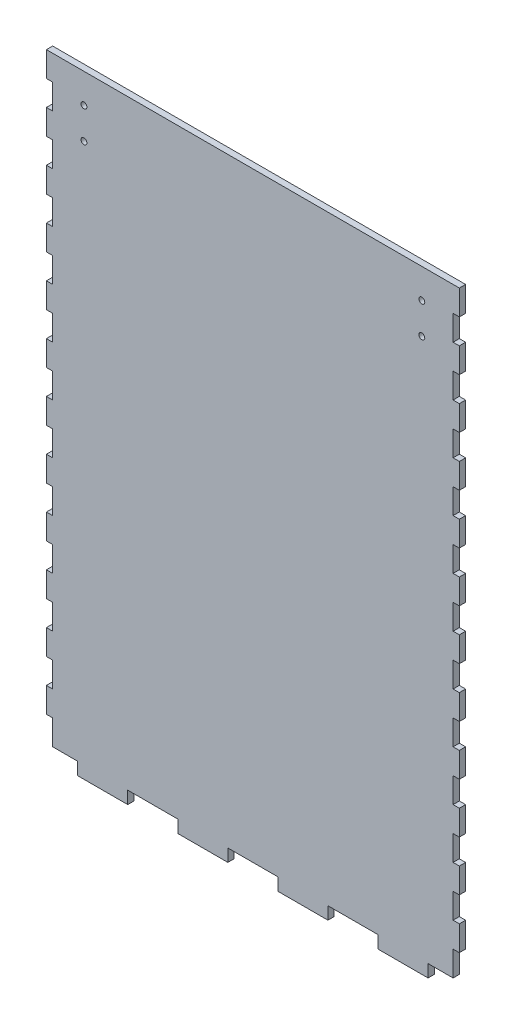
SolidWorks part; units mm, degrees
ref_plane "Front Plane" through (0, 0, 0) normal (0, 0, 1) x (1, 0, 0)
ref_plane "Top Plane" through (0, 0, 0) normal (0, 1, 0) x (1, 0, 0)
ref_plane "Right Plane" through (0, 0, 0) normal (1, 0, 0) x (0, 0, -1)
sketch "Sketch1" plane through (0, 0, 0) normal (0, 0, 1) x (1, 0, 0)
  line L0 (0, 0) -> (203.2, 0)
  line L1 (203.2, 0) -> (203.2, 304.8)
  line L2 (203.2, 304.8) -> (0, 304.8)
  line L3 (0, 304.8) -> (0, 0)
  dimension "D1" = 203.2
  dimension "D2" = 304.8
extrude "Boss-Extrude1" add sketch "Sketch1" along normal blind 3.175
sketch "Sketch2" plane through (0, 0, 3.175) normal (0, 0, 1) x (1, 0, 0)
  line L0 (0, 304.8) -> (-3.175, 304.8)
  line L1 (-3.175, 304.8) -> (-3.175, 292.1)
  line L2 (-3.175, 292.1) -> (0, 292.1)
  line L3 (0, 304.8) -> (0, 0) construction
  line L4 (0, 292.1) -> (0, 304.8)
  line L5 (101.6, 304.8) -> (101.6, 0) construction
  line L6 (203.2, 304.8) -> (0, 304.8) construction
  line L7 (0, 0) -> (203.2, 0) construction
  line L8 (206.375, 292.1) -> (203.2, 292.1)
  line L9 (206.375, 304.8) -> (206.375, 292.1)
  line L10 (203.2, 304.8) -> (206.375, 304.8)
  line L11 (203.2, 292.1) -> (203.2, 304.8)
  line L12 (0, 266.7) -> (0, 279.4)
  line L13 (0, 279.4) -> (-3.175, 279.4)
  line L14 (-3.175, 279.4) -> (-3.175, 266.7)
  line L15 (-3.175, 266.7) -> (0, 266.7)
  line L16 (206.375, 266.7) -> (203.2, 266.7)
  line L17 (203.2, 266.7) -> (203.2, 279.4)
  line L18 (203.2, 279.4) -> (206.375, 279.4)
  line L19 (206.375, 279.4) -> (206.375, 266.7)
  line L20 (0, 241.3) -> (0, 254)
  line L21 (0, 254) -> (-3.175, 254)
  line L22 (-3.175, 254) -> (-3.175, 241.3)
  line L23 (-3.175, 241.3) -> (0, 241.3)
  line L24 (206.375, 241.3) -> (203.2, 241.3)
  line L25 (203.2, 241.3) -> (203.2, 254)
  line L26 (203.2, 254) -> (206.375, 254)
  line L27 (206.375, 254) -> (206.375, 241.3)
  line L28 (0, 215.9) -> (0, 228.6)
  line L29 (0, 228.6) -> (-3.175, 228.6)
  line L30 (-3.175, 228.6) -> (-3.175, 215.9)
  line L31 (-3.175, 215.9) -> (0, 215.9)
  line L32 (206.375, 215.9) -> (203.2, 215.9)
  line L33 (203.2, 215.9) -> (203.2, 228.6)
  line L34 (203.2, 228.6) -> (206.375, 228.6)
  line L35 (206.375, 228.6) -> (206.375, 215.9)
  line L36 (0, 190.5) -> (0, 203.2)
  line L37 (0, 203.2) -> (-3.175, 203.2)
  line L38 (-3.175, 203.2) -> (-3.175, 190.5)
  line L39 (-3.175, 190.5) -> (0, 190.5)
  line L40 (206.375, 190.5) -> (203.2, 190.5)
  line L41 (203.2, 190.5) -> (203.2, 203.2)
  line L42 (203.2, 203.2) -> (206.375, 203.2)
  line L43 (206.375, 203.2) -> (206.375, 190.5)
  line L44 (0, 165.1) -> (0, 177.8)
  line L45 (0, 177.8) -> (-3.175, 177.8)
  line L46 (-3.175, 177.8) -> (-3.175, 165.1)
  line L47 (-3.175, 165.1) -> (0, 165.1)
  line L48 (206.375, 165.1) -> (203.2, 165.1)
  line L49 (203.2, 165.1) -> (203.2, 177.8)
  line L50 (203.2, 177.8) -> (206.375, 177.8)
  line L51 (206.375, 177.8) -> (206.375, 165.1)
  line L52 (0, 139.7) -> (0, 152.4)
  line L53 (0, 152.4) -> (-3.175, 152.4)
  line L54 (-3.175, 152.4) -> (-3.175, 139.7)
  line L55 (-3.175, 139.7) -> (0, 139.7)
  line L56 (206.375, 139.7) -> (203.2, 139.7)
  line L57 (203.2, 139.7) -> (203.2, 152.4)
  line L58 (203.2, 152.4) -> (206.375, 152.4)
  line L59 (206.375, 152.4) -> (206.375, 139.7)
  line L60 (0, 114.3) -> (0, 127)
  line L61 (0, 127) -> (-3.175, 127)
  line L62 (-3.175, 127) -> (-3.175, 114.3)
  line L63 (-3.175, 114.3) -> (0, 114.3)
  line L64 (206.375, 114.3) -> (203.2, 114.3)
  line L65 (203.2, 114.3) -> (203.2, 127)
  line L66 (203.2, 127) -> (206.375, 127)
  line L67 (206.375, 127) -> (206.375, 114.3)
  line L68 (0, 88.9) -> (0, 101.6)
  line L69 (0, 101.6) -> (-3.175, 101.6)
  line L70 (-3.175, 101.6) -> (-3.175, 88.9)
  line L71 (-3.175, 88.9) -> (0, 88.9)
  line L72 (206.375, 88.9) -> (203.2, 88.9)
  line L73 (203.2, 88.9) -> (203.2, 101.6)
  line L74 (203.2, 101.6) -> (206.375, 101.6)
  line L75 (206.375, 101.6) -> (206.375, 88.9)
  line L76 (0, 63.5) -> (0, 76.2)
  line L77 (0, 76.2) -> (-3.175, 76.2)
  line L78 (-3.175, 76.2) -> (-3.175, 63.5)
  line L79 (-3.175, 63.5) -> (0, 63.5)
  line L80 (206.375, 63.5) -> (203.2, 63.5)
  line L81 (203.2, 63.5) -> (203.2, 76.2)
  line L82 (203.2, 76.2) -> (206.375, 76.2)
  line L83 (206.375, 76.2) -> (206.375, 63.5)
  line L84 (0, 38.1) -> (0, 50.8)
  line L85 (0, 50.8) -> (-3.175, 50.8)
  line L86 (-3.175, 50.8) -> (-3.175, 38.1)
  line L87 (-3.175, 38.1) -> (0, 38.1)
  line L88 (206.375, 38.1) -> (203.2, 38.1)
  line L89 (203.2, 38.1) -> (203.2, 50.8)
  line L90 (203.2, 50.8) -> (206.375, 50.8)
  line L91 (206.375, 50.8) -> (206.375, 38.1)
  line L92 (0, 12.7) -> (0, 25.4)
  line L93 (0, 25.4) -> (-3.175, 25.4)
  line L94 (-3.175, 25.4) -> (-3.175, 12.7)
  line L95 (-3.175, 12.7) -> (0, 12.7)
  line L96 (206.375, 12.7) -> (203.2, 12.7)
  line L97 (203.2, 12.7) -> (203.2, 25.4)
  line L98 (203.2, 25.4) -> (206.375, 25.4)
  line L99 (206.375, 25.4) -> (206.375, 12.7)
  line L100 (0, 292.1) -> (0, 266.7) construction
  line L101 (12.7, 0) -> (12.7, -6.35)
  line L102 (12.7, -6.35) -> (38.1, -6.35)
  line L103 (38.1, -6.35) -> (38.1, 0)
  line L104 (38.1, 0) -> (12.7, 0)
  line L105 (88.9, 0) -> (63.5, 0)
  line L106 (63.5, 0) -> (63.5, -6.35)
  line L107 (63.5, -6.35) -> (88.9, -6.35)
  line L108 (88.9, -6.35) -> (88.9, 0)
  line L109 (139.7, 0) -> (114.3, 0)
  line L110 (114.3, 0) -> (114.3, -6.35)
  line L111 (114.3, -6.35) -> (139.7, -6.35)
  line L112 (139.7, -6.35) -> (139.7, 0)
  line L113 (190.5, 0) -> (165.1, 0)
  line L114 (165.1, 0) -> (165.1, -6.35)
  line L115 (165.1, -6.35) -> (190.5, -6.35)
  line L116 (190.5, -6.35) -> (190.5, 0)
  line L117 (38.1, 0) -> (88.9, 0) construction
  dimension "D1" = 3.175
  dimension "D2" = 12.7
  dimension "D4" = 25.4
  dimension "D5" = 12.7
  dimension "D6" = 6.35
  dimension "D7" = 25.4
  dimension "D9" = 50.8
  dimension "D3" = 12
  dimension "D8" = 4
extrude "Boss-Extrude2" add sketch "Sketch2" against normal up to surface (3.175 mm away) up to face at (101.6, 152.4, 0)
sketch "Sketch3" [suppressed] plane through (0, 0, 3.175) normal (0, 0, 1) x (1, 0, 0)
  line L0 (0, 0) -> (-3.175, 0)
  line L1 (-3.175, 0) -> (-3.175, 12.7)
  line L2 (-3.175, 12.7) -> (0, 12.7)
  line L3 (0, 304.8) -> (0, 0) construction
  line L4 (0, 12.7) -> (0, 0)
  line L5 (101.6, 304.8) -> (101.6, 0) construction
  line L6 (203.2, 304.8) -> (0, 304.8) construction
  line L7 (0, 0) -> (203.2, 0) construction
  line L8 (206.375, 12.7) -> (203.2, 12.7)
  line L9 (206.375, 0) -> (206.375, 12.7)
  line L10 (203.2, 0) -> (206.375, 0)
  line L11 (203.2, 12.7) -> (203.2, 0)
  line L12 (0, 38.1) -> (0, 25.4)
  line L13 (0, 25.4) -> (-3.175, 25.4)
  line L14 (-3.175, 25.4) -> (-3.175, 38.1)
  line L15 (-3.175, 38.1) -> (0, 38.1)
  line L16 (206.375, 38.1) -> (203.2, 38.1)
  line L17 (203.2, 38.1) -> (203.2, 25.4)
  line L18 (203.2, 25.4) -> (206.375, 25.4)
  line L19 (206.375, 25.4) -> (206.375, 38.1)
  line L20 (0, 63.5) -> (0, 50.8)
  line L21 (0, 50.8) -> (-3.175, 50.8)
  line L22 (-3.175, 50.8) -> (-3.175, 63.5)
  line L23 (-3.175, 63.5) -> (0, 63.5)
  line L24 (206.375, 63.5) -> (203.2, 63.5)
  line L25 (203.2, 63.5) -> (203.2, 50.8)
  line L26 (203.2, 50.8) -> (206.375, 50.8)
  line L27 (206.375, 50.8) -> (206.375, 63.5)
  line L28 (0, 88.9) -> (0, 76.2)
  line L29 (0, 76.2) -> (-3.175, 76.2)
  line L30 (-3.175, 76.2) -> (-3.175, 88.9)
  line L31 (-3.175, 88.9) -> (0, 88.9)
  line L32 (206.375, 88.9) -> (203.2, 88.9)
  line L33 (203.2, 88.9) -> (203.2, 76.2)
  line L34 (203.2, 76.2) -> (206.375, 76.2)
  line L35 (206.375, 76.2) -> (206.375, 88.9)
  line L36 (0, 114.3) -> (0, 101.6)
  line L37 (0, 101.6) -> (-3.175, 101.6)
  line L38 (-3.175, 101.6) -> (-3.175, 114.3)
  line L39 (-3.175, 114.3) -> (0, 114.3)
  line L40 (206.375, 114.3) -> (203.2, 114.3)
  line L41 (203.2, 114.3) -> (203.2, 101.6)
  line L42 (203.2, 101.6) -> (206.375, 101.6)
  line L43 (206.375, 101.6) -> (206.375, 114.3)
  line L44 (0, 139.7) -> (0, 127)
  line L45 (0, 127) -> (-3.175, 127)
  line L46 (-3.175, 127) -> (-3.175, 139.7)
  line L47 (-3.175, 139.7) -> (0, 139.7)
  line L48 (206.375, 139.7) -> (203.2, 139.7)
  line L49 (203.2, 139.7) -> (203.2, 127)
  line L50 (203.2, 127) -> (206.375, 127)
  line L51 (206.375, 127) -> (206.375, 139.7)
  line L52 (0, 165.1) -> (0, 152.4)
  line L53 (0, 152.4) -> (-3.175, 152.4)
  line L54 (-3.175, 152.4) -> (-3.175, 165.1)
  line L55 (-3.175, 165.1) -> (0, 165.1)
  line L56 (206.375, 165.1) -> (203.2, 165.1)
  line L57 (203.2, 165.1) -> (203.2, 152.4)
  line L58 (203.2, 152.4) -> (206.375, 152.4)
  line L59 (206.375, 152.4) -> (206.375, 165.1)
  line L60 (0, 190.5) -> (0, 177.8)
  line L61 (0, 177.8) -> (-3.175, 177.8)
  line L62 (-3.175, 177.8) -> (-3.175, 190.5)
  line L63 (-3.175, 190.5) -> (0, 190.5)
  line L64 (206.375, 190.5) -> (203.2, 190.5)
  line L65 (203.2, 190.5) -> (203.2, 177.8)
  line L66 (203.2, 177.8) -> (206.375, 177.8)
  line L67 (206.375, 177.8) -> (206.375, 190.5)
  line L68 (0, 215.9) -> (0, 203.2)
  line L69 (0, 203.2) -> (-3.175, 203.2)
  line L70 (-3.175, 203.2) -> (-3.175, 215.9)
  line L71 (-3.175, 215.9) -> (0, 215.9)
  line L72 (206.375, 215.9) -> (203.2, 215.9)
  line L73 (203.2, 215.9) -> (203.2, 203.2)
  line L74 (203.2, 203.2) -> (206.375, 203.2)
  line L75 (206.375, 203.2) -> (206.375, 215.9)
  line L76 (0, 241.3) -> (0, 228.6)
  line L77 (0, 228.6) -> (-3.175, 228.6)
  line L78 (-3.175, 228.6) -> (-3.175, 241.3)
  line L79 (-3.175, 241.3) -> (0, 241.3)
  line L80 (206.375, 241.3) -> (203.2, 241.3)
  line L81 (203.2, 241.3) -> (203.2, 228.6)
  line L82 (203.2, 228.6) -> (206.375, 228.6)
  line L83 (206.375, 228.6) -> (206.375, 241.3)
  line L84 (0, 266.7) -> (0, 254)
  line L85 (0, 254) -> (-3.175, 254)
  line L86 (-3.175, 254) -> (-3.175, 266.7)
  line L87 (-3.175, 266.7) -> (0, 266.7)
  line L88 (206.375, 266.7) -> (203.2, 266.7)
  line L89 (203.2, 266.7) -> (203.2, 254)
  line L90 (203.2, 254) -> (206.375, 254)
  line L91 (206.375, 254) -> (206.375, 266.7)
  line L92 (0, 292.1) -> (0, 279.4)
  line L93 (0, 279.4) -> (-3.175, 279.4)
  line L94 (-3.175, 279.4) -> (-3.175, 292.1)
  line L95 (-3.175, 292.1) -> (0, 292.1)
  line L96 (206.375, 292.1) -> (203.2, 292.1)
  line L97 (203.2, 292.1) -> (203.2, 279.4)
  line L98 (203.2, 279.4) -> (206.375, 279.4)
  line L99 (206.375, 279.4) -> (206.375, 292.1)
  line L100 (0, 12.7) -> (0, 38.1) construction
  line L101 (12.7, 0) -> (12.7, -6.35)
  line L102 (12.7, -6.35) -> (38.1, -6.35)
  line L103 (38.1, -6.35) -> (38.1, 0)
  line L104 (38.1, 0) -> (12.7, 0)
  line L105 (88.9, 0) -> (63.5, 0)
  line L106 (63.5, 0) -> (63.5, -6.35)
  line L107 (63.5, -6.35) -> (88.9, -6.35)
  line L108 (88.9, -6.35) -> (88.9, 0)
  line L109 (139.7, 0) -> (114.3, 0)
  line L110 (114.3, 0) -> (114.3, -6.35)
  line L111 (114.3, -6.35) -> (139.7, -6.35)
  line L112 (139.7, -6.35) -> (139.7, 0)
  line L113 (190.5, 0) -> (165.1, 0)
  line L114 (165.1, 0) -> (165.1, -6.35)
  line L115 (165.1, -6.35) -> (190.5, -6.35)
  line L116 (190.5, -6.35) -> (190.5, 0)
  line L117 (38.1, 0) -> (88.9, 0) construction
  dimension "D1" = 3.175
  dimension "D2" = 12.7
  dimension "D9" = 50.8
  dimension "D3" = 12
  dimension "D8" = 4
  dimension "D4" = 25.4
  dimension "D5" = 6.35
  dimension "D6" = 25.4
  dimension "D7" = 12.7
sketch "Sketch4" plane through (0, 0, 3.175) normal (0, 0, 1) x (1, 0, 0)
  line L0 (60, 33.5) -> (60, 66.5) construction
  line L1 (43.5, 50) -> (76.5, 50) construction
  line L2 (0, 12.7) -> (0, 0) construction
  line L3 (88.9, 0) -> (114.3, 0) construction
  circle A0 centre (60, 50) radius 16.5
  circle A1 centre (35, 75) radius 1.5
  circle A5 centre (85, 75) radius 1.5
  circle A6 centre (85, 25) radius 1.5
  circle A7 centre (35, 25) radius 1.5
  dimension "D5" = 33
  dimension "D6" = 3
  dimension "D1" = 50
  dimension "D2" = 50
  dimension "D3" = 60
  dimension "D4" = 50
extrude "Cut-Extrude1" [suppressed] cut sketch "Sketch4" against normal up to surface (3.175 mm away) up to face at (101.6, 130.175, 0)
sketch "Sketch5" plane through (0, 0, 0) normal (0, 0, -1) x (-1, 0, 0)
  line L1 (-206.375, 304.8) -> (-206.375, 292.1) construction
  line L2 (-206.375, 304.8) -> (3.175, 304.8) construction
  line L3 (-101.6, 304.8) -> (-101.6, 0) construction
  line L4 (-88.9, 0) -> (-114.3, 0) construction
  circle A1 centre (-187.325, 289.8) radius 1.5
  circle A2 centre (-187.325, 274.05) radius 1.5
  circle A3 centre (-15.875, 274.05) radius 1.5
  circle A4 centre (-15.875, 289.8) radius 1.5
  dimension "D1" = 3
  dimension "D2" = 3
  dimension "D3" = 15.75
  dimension "D4" = 19.05
  dimension "D5" = 15
extrude "Cut-Extrude2" cut sketch "Sketch5" against normal up to surface (3.175 mm away) up to face at (101.6, 130.175, 3.175)
extrude "Boss-Extrude4" [suppressed] add sketch "Sketch3" against normal up to surface (3.175 mm away) up to face at (17.375, 289.8, 0)
sketch "Sketch6" [suppressed] plane through (0, 0, 0) normal (0, 0, -1) x (-1, 0, 0)
  line L1 (-203.2, 304.8) -> (0, 304.8) construction
  line L2 (-101.6, 304.8) -> (-101.6, 0) construction
  line L3 (-88.9, 0) -> (-114.3, 0) construction
  line L4 (-206.375, 292.1) -> (-206.375, 279.4) construction
  circle A0 centre (-187.325, 289.8) radius 1.5
  circle A1 centre (-187.325, 274.05) radius 1.5
  circle A2 centre (-15.875, 274.05) radius 1.5
  circle A3 centre (-15.875, 289.8) radius 1.5
  dimension "D1" = 3
  dimension "D2" = 3
  dimension "D3" = 19.05
  dimension "D4" = 15
  dimension "D5" = 15.75
extrude "Cut-Extrude3" [suppressed] cut sketch "Sketch6" against normal up to surface (3.175 mm away) up to face at (17.375, 289.8, 3.175)
equation "\"wall_thickness\"= 0.125in"
equation "\"base_thickness\"= 0.25in"
equation "\"D1@Boss-Extrude1\"=\"wall_thickness\""
equation "\"D1@Sketch2\"=\"wall_thickness\""
equation "\"D6@Sketch2\"=\"base_thickness\""
equation "\"D1@Sketch3\"=\"wall_thickness\""
equation "\"D5@Sketch3\"=\"base_thickness\""
